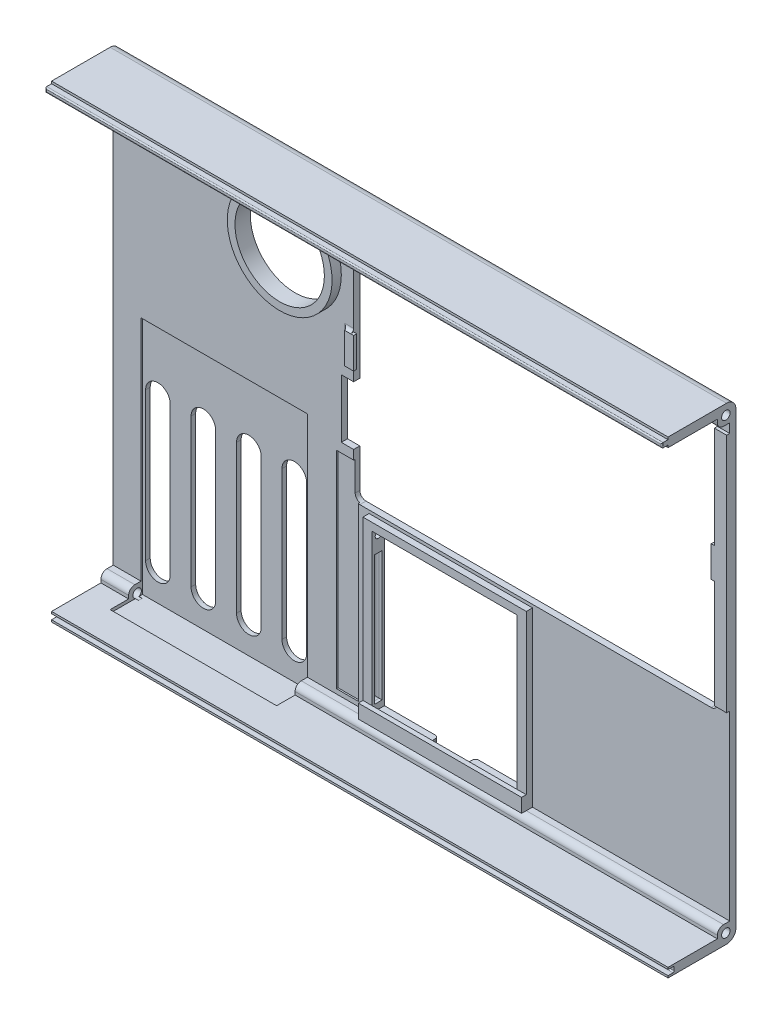
SolidWorks part; units mm, degrees
ref_plane "Front Plane" through (0, 0, 0) normal (0, 0, 1) x (1, 0, 0)
ref_plane "Top Plane" through (0, 0, 0) normal (0, 1, 0) x (1, 0, 0)
ref_plane "Right Plane" through (0, 0, 0) normal (1, 0, 0) x (0, 0, -1)
sketch "Sketch1" plane through (0, 0, 0) normal (0, 0, 1) x (1, 0, 0)
  line L1 (105, -90.3987) -> (-95, -90.3987)
  line L2 (105, -90.3987) -> (105, 61.6013)
  line L3 (105, 61.6013) -> (-95, 61.6013)
  line L4 (-95, -90.3987) -> (-95, 61.6013)
  line L5 (105, -90.3987) -> (-95, 61.6013) construction
  line L6 (105, 61.6013) -> (-95, -90.3987) construction
  point P0 (5, -14.3987)
  dimension "D1" = 200
  dimension "D2" = 152
extrude "body" add sketch "Sketch1" along normal blind 2
sketch "Sketch3" plane through (0, 0, 0) normal (0, 0, -1) x (-1, 0, 0)
  line L0 (95, -54.3987) -> (-105, -54.3987) construction
  line L1 (95, 61.6013) -> (95, -90.3987) construction
  line L2 (-105, -90.3987) -> (-105, 61.6013) construction
  line L3 (66.25, -78.3987) -> (66.25, -30.3987) construction
  line L4 (62.25, -78.3987) -> (62.25, -30.3987)
  line L5 (70.25, -78.3987) -> (70.25, -30.3987)
  line L6 (95, -30.3987) -> (-105, -30.3987) construction
  line L7 (81, -78.3987) -> (81, -30.3987) construction
  line L8 (95, -78.3987) -> (-105, -78.3987) construction
  line L9 (77, -78.3987) -> (77, -30.3987)
  line L10 (85, -78.3987) -> (85, -30.3987)
  line L11 (51.5, -78.3987) -> (51.5, -30.3987) construction
  line L12 (47.5, -78.3987) -> (47.5, -30.3987)
  line L13 (55.5, -78.3987) -> (55.5, -30.3987)
  line L14 (36.75, -78.3987) -> (36.75, -30.3987) construction
  line L15 (32.75, -78.3987) -> (32.75, -30.3987)
  line L16 (40.75, -78.3987) -> (40.75, -30.3987)
  line L17 (95, -90.3987) -> (95, 61.6013) construction
  line L18 (-105, 61.6013) -> (95, 61.6013) construction
  line L19 (95, -90.3987) -> (-105, -90.3987) construction
  line L20 (-105, -90.3987) -> (-105, 61.6013) construction
  circle A0 centre (38, 34.1013) radius 14.5
  arc A1 (62.25, -78.3987) -> (70.25, -78.3987) centre (66.25, -78.3987) ccw
  arc A2 (70.25, -30.3987) -> (62.25, -30.3987) centre (66.25, -30.3987) ccw
  arc A3 (77, -78.3987) -> (85, -78.3987) centre (81, -78.3987) ccw
  arc A4 (85, -30.3987) -> (77, -30.3987) centre (81, -30.3987) ccw
  arc A5 (47.5, -78.3987) -> (55.5, -78.3987) centre (51.5, -78.3987) ccw
  arc A6 (55.5, -30.3987) -> (47.5, -30.3987) centre (51.5, -30.3987) ccw
  arc A7 (32.75, -78.3987) -> (40.75, -78.3987) centre (36.75, -78.3987) ccw
  arc A8 (40.75, -30.3987) -> (32.75, -30.3987) centre (36.75, -30.3987) ccw
  point P10 (66.25, -54.3987)
  point P21 (81, -54.3987)
  point P27 (51.5, -54.3987)
  point P34 (36.75, -54.3987)
  dimension "D1" = 29
  dimension "D2" = 27.5
  dimension "D3" = 57
  dimension "D4" = 10
  dimension "D5" = 12
  dimension "D6" = 24
  dimension "D7" = 6.75
  dimension "D8" = 8
  dimension "D9" = 8
  dimension "D10" = 8
  dimension "D11" = 8
  dimension "D12" = 6.75
  dimension "D13" = 52.25
  dimension "D14" = 6.75
extrude "fan_exhaust_grill" cut sketch "Sketch3" against normal through all
sketch "Sketch12" plane through (0, 0, 2) normal (0, 0, 1) x (1, 0, 0)
  line L0 (-95, -90.3987) -> (-95, 61.6013) construction
  line L1 (105, -90.3987) -> (-95, -90.3987)
  line L2 (105, -90.3987) -> (105, -84.3987)
  line L3 (105, -84.3987) -> (-95, -84.3987)
  line L4 (-95, -90.3987) -> (-95, -84.3987)
  line L6 (105, 61.6013) -> (-95, 61.6013)
  line L7 (105, 61.6013) -> (105, 55.6013)
  line L8 (105, 55.6013) -> (-95, 55.6013)
  line L9 (-95, 61.6013) -> (-95, 55.6013)
  dimension "D1" = 6
  dimension "D2" = 6
extrude "side_walls" add sketch "Sketch12" along normal blind 20
sketch "Sketch14" plane through (105, 0, 0) normal (1, 0, 0) x (0, 0, -1)
  line L0 (-22, -90.3987) -> (0, -90.3987) construction
  line L1 (0, -90.3987) -> (0, 61.6013) construction
  line L2 (-22, 61.6013) -> (0, 61.6013) construction
  circle A0 centre (-3.25, -87.1487) radius 1.375
  circle A1 centre (-3.25, 58.3513) radius 1.375
  dimension "D1" = 2.75
  dimension "D2" = 2.75
  dimension "D3" = 3.25
  dimension "D4" = 3.25
  dimension "D5" = 3.25
  dimension "D6" = 3.25
  dimension "D7" = 145.5
extrude "mount_holes_l" cut sketch "Sketch14" against normal blind 10 and the other way through all
sketch "Sketch16" plane through (-95, 0, 0) normal (-1, 0, 0) x (0, 0, 1)
  line L0 (0, -90.3987) -> (0, 61.6013) construction
  line L2 (22, 61.6013) -> (0, 61.6013) construction
  line L3 (22, -90.3987) -> (0, -90.3987) construction
  circle A0 centre (3.25, -87.1487) radius 1.375
  circle A1 centre (3.25, 58.3513) radius 1.375
  dimension "D1" = 2.75
  dimension "D4" = 2.75
  dimension "D2" = 3.25
  dimension "D3" = 3.25
  dimension "D5" = 3.25
  dimension "D6" = 3.25
extrude "mount_holes_r" cut sketch "Sketch16" against normal blind 10
sketch "Sketch18" plane through (105, 0, 0) normal (1, 0, 0) x (0, 0, -1)
  line L1 (-22, -84.3987) -> (-6, -84.3987)
  line L2 (-22, -84.3987) -> (-22, -87.3987)
  line L3 (-22, -87.3987) -> (-6, -87.3987)
  line L4 (-6, -84.3987) -> (-6, -87.3987)
  line L5 (-22, 55.6013) -> (-6, 55.6013)
  line L6 (-22, 55.6013) -> (-22, 58.6013)
  line L7 (-22, 58.6013) -> (-6, 58.6013)
  line L8 (-6, 55.6013) -> (-6, 58.6013)
  dimension "D1" = 3
  dimension "D2" = 16
  dimension "D3" = 3
  dimension "D4" = 16
extrude "wall_reduce" cut sketch "Sketch18" against normal through all
sketch "Sketch19" plane through (0, 0, 22) normal (0, 0, 1) x (1, 0, 0)
  line L0 (-95, -90.3987) -> (-95, 61.6013) construction
  line L1 (-95, -89.7487) -> (105, -89.7487)
  line L2 (-95, -89.7487) -> (-95, -88.0487)
  line L3 (-95, -88.0487) -> (105, -88.0487)
  line L4 (105, -89.7487) -> (105, -88.0487)
  line L5 (105, -90.3987) -> (105, 61.6013) construction
  line L6 (-95, -90.3987) -> (105, -90.3987) construction
  line L7 (-95, -87.3987) -> (105, -87.3987) construction
  dimension "D1" = 0.65
  dimension "D2" = 1.7
  dimension "D3" = 0.65
extrude "groove" cut sketch "Sketch19" against normal blind 2
sketch "Sketch20" plane through (0, 0, 22) normal (0, 0, 1) x (1, 0, 0)
  line L0 (-95, -90.3987) -> (-95, 61.6013) construction
  line L1 (-95, 59.3513) -> (105, 59.3513)
  line L2 (-95, 59.3513) -> (-95, 60.8513)
  line L3 (-95, 60.8513) -> (105, 60.8513)
  line L4 (105, 59.3513) -> (105, 60.8513)
  line L5 (105, -90.3987) -> (105, 61.6013) construction
  line L6 (105, 61.6013) -> (-95, 61.6013) construction
  dimension "D1" = 0.75
  dimension "D2" = 1.5
extrude "notch" add sketch "Sketch20" along normal blind 2
sketch "Sketch21" plane through (0, 0, 2) normal (0, 0, 1) x (1, 0, 0)
  line L0 (105, -90.3987) -> (105, 61.6013) construction
  line L1 (101, -27.3987) -> (-17, -27.3987)
  line L2 (101, -27.3987) -> (101, 55.1013)
  line L3 (101, 55.1013) -> (-17, 55.1013)
  line L4 (-17, -27.3987) -> (-17, 55.1013)
  line L5 (105, 61.6013) -> (-95, 61.6013) construction
  dimension "D1" = 118
  dimension "D2" = 82.5
  dimension "D3" = 4
  dimension "D4" = 6.5
extrude "batt_cut" cut sketch "Sketch21" against normal through all
fillet "Fillet1" radius 3 2 edges at (5, -90.3987, 0) (5, 61.6013, 0)
fillet "Fillet2" radius 2 2 edges at (5, -84.3987, 6) (5, 55.6013, 6)
fillet "Fillet3" radius 0.4 6 edges at (5, 60.8513, 24) (105, 60.1013, 24) (5, 59.3513, 24) (-95, 60.1013, 24) (5, -89.7487, 20) (5, -88.0487, 20)
fillet "Fillet4" radius 2 4 edges at (-17, -27.3987, 1) (101, -27.3987, 1) (101, 55.1013, 1) (-17, 55.1013, 1)
sketch "Sketch22" plane through (0, 0, 2) normal (0, 0, 1) x (1, 0, 0)
  circle A0 centre (-38, 34.1013) radius 14.5
  circle A1 centre (-38, 34.1013) radius 17
  dimension "D1" = 29
  dimension "D2" = 34
extrude "fan_hole_supp" add sketch "Sketch22" along normal blind 3
sketch "Sketch23" plane through (0, 0, 2) normal (0, 0, 1) x (1, 0, 0)
  line L0 (105, -90.3987) -> (105, 61.6013) construction
  line L1 (105, 52.6013) -> (101, 52.6013)
  line L2 (105, 52.6013) -> (105, -25.3987)
  line L3 (105, -25.3987) -> (101, -25.3987)
  line L4 (101, 52.6013) -> (101, -25.3987)
  arc A0 (99, -27.3987) -> (101, -25.3987) centre (99, -25.3987) ccw construction
  dimension "D1" = 78
  dimension "D2" = 4
extrude "batt_cut_supp" add sketch "Sketch23" along normal blind 1
sketch "Sketch24" plane through (0, 0, 2) normal (0, 0, 1) x (1, 0, 0)
  line L0 (-95, -90.3987) -> (-95, 61.6013) construction
  line L1 (-86, -10.3987) -> (-32, -10.3987)
  line L2 (-86, -10.3987) -> (-86, -88.3987)
  line L3 (-86, -88.3987) -> (-32, -88.3987)
  line L4 (-32, -10.3987) -> (-32, -88.3987)
  line L5 (-95, -90.3987) -> (105, -90.3987) construction
  line L7 (-22.5, -15.8987) -> (-15.5, -15.8987)
  line L8 (-22.5, -15.8987) -> (-22.5, -82.8987)
  line L9 (-22.5, -82.8987) -> (-15.5, -82.8987)
  line L10 (-15.5, -15.8987) -> (-15.5, -82.8987)
  dimension "D1" = 9
  dimension "D2" = 2
  dimension "D3" = 54
  dimension "D4" = 78
  dimension "D5" = 9.5
  dimension "D6" = 7
  dimension "D7" = 67
  dimension "D8" = 5.5
  dimension "D9" = 5.5
extrude "Cut-Extrude1" cut sketch "Sketch24" against normal blind 10.5 from offset 10
sketch "Sketch25" plane through (0, 0, 2) normal (0, 0, 1) x (1, 0, 0)
  line L7 (-17, 53.1013) -> (-17, -15.8987) construction
  line L8 (-17, 6.1013) -> (-21, 6.1013)
  line L9 (-17, 6.1013) -> (-17, -12.8987)
  line L10 (-17, -12.8987) -> (-21, -12.8987)
  line L11 (-21, 6.1013) -> (-21, -12.8987)
  line L12 (-15, -27.3987) -> (99, -27.3987) construction
  dimension "D1" = 14.5
  dimension "D2" = 19
  dimension "D3" = 4
extrude "Cut-Extrude2" cut sketch "Sketch25" against normal through all
sketch "Sketch26" plane through (0, 0, 2) normal (0, 0, 1) x (1, 0, 0)
  line L0 (-17, 53.1013) -> (-17, 6.1013) construction
  line L1 (-17, 20.1013) -> (-19, 20.1013)
  line L2 (-17, 20.1013) -> (-17, 10.1013)
  line L3 (-17, 10.1013) -> (-19, 10.1013)
  line L4 (-19, 20.1013) -> (-19, 10.1013)
  line L10 (99, 55.1013) -> (-15, 55.1013) construction
  dimension "D4" = 2
  dimension "D5" = 10
  dimension "D6" = 35
extrude "Boss-Extrude1" add sketch "Sketch26" along normal blind 1
sketch "Sketch27" plane through (-17, 0, 0) normal (1, 0, 0) x (0, 0, -1)
  line L0 (-3, 10.1013) -> (-3, 20.1013) construction
  line L1 (-3, 20.1013) -> (-2, 20.1013)
  line L2 (-3, 20.1013) -> (-3, 10.1013)
  line L3 (-3, 10.1013) -> (-2, 10.1013)
  line L4 (-2, 20.1013) -> (-2, 10.1013)
  line L5 (-3, 20.1013) -> (-2, 20.1013) construction
extrude "Boss-Extrude2" add sketch "Sketch27" along normal blind 1
sketch "Sketch28" plane through (101, 0, 0) normal (-1, 0, 0) x (0, 0, 1)
  line L0 (0, -25.3987) -> (0, 53.1013) construction
  line L1 (2, 9.6013) -> (3, 9.6013)
  line L2 (2, 9.6013) -> (2, 19.6013)
  line L3 (2, 19.6013) -> (3, 19.6013)
  line L4 (3, 9.6013) -> (3, 19.6013)
  line L5 (3, 52.6013) -> (2, 52.6013) construction
  dimension "D1" = 1
  dimension "D2" = 2
  dimension "D3" = 10
  dimension "D4" = 33
extrude "Boss-Extrude3" add sketch "Sketch28" along normal blind 1
fillet "Fillet5" radius 1 3 edges at (-18, 20.1013, 2) (-18, 10.1013, 2) (-19, 15.1013, 2)
sketch "Sketch29" plane through (0, 0, 2) normal (0, 0, 1) x (1, 0, 0)
  line L1 (-9, -30.8987) -> (38, -30.8987)
  line L2 (-9, -30.8987) -> (-9, -81.8987)
  line L3 (-9, -81.8987) -> (38, -81.8987)
  line L4 (38, -30.8987) -> (38, -81.8987)
  line L5 (105, -90.3987) -> (105, 61.6013) construction
  line L7 (-95, -90.3987) -> (105, -90.3987) construction
  dimension "D1" = 67
  dimension "D2" = 47
  dimension "D3" = 51
  dimension "D4" = 8.5
extrude "stand_cut" cut sketch "Sketch29" against normal through all
sketch "Sketch30" plane through (0, 0, 2) normal (0, 0, 1) x (1, 0, 0)
  line L0 (-9, -81.8987) -> (38, -30.8987) construction
  line L1 (38, -30.8987) -> (-9, -30.8987) construction
  line L2 (38, -81.8987) -> (38, -30.8987) construction
  line L3 (-9, -30.8987) -> (38, -81.8987) construction
  line L5 (41, -84.3987) -> (-12, -84.3987)
  line L6 (41, -84.3987) -> (41, -28.3987)
  line L7 (41, -28.3987) -> (-12, -28.3987)
  line L8 (-12, -84.3987) -> (-12, -28.3987)
  line L9 (41, -84.3987) -> (-12, -28.3987) construction
  line L10 (41, -28.3987) -> (-12, -84.3987) construction
  line L11 (38, -81.8987) -> (-9, -81.8987)
  line L12 (38, -81.8987) -> (38, -30.8987)
  line L13 (38, -30.8987) -> (-9, -30.8987)
  line L14 (-9, -81.8987) -> (-9, -30.8987)
  line L15 (38, -81.8987) -> (-9, -30.8987) construction
  line L16 (38, -30.8987) -> (-9, -81.8987) construction
  point P11 (14.5, -56.3987)
  point P16 (14.5, -56.3987)
  dimension "D1" = 3
  dimension "D2" = 2.5
extrude "stand_extra_support" add sketch "Sketch30" along normal blind 2
sketch "Sketch31" plane through (-9, 0, 0) normal (1, 0, 0) x (0, 0, -1)
  line L0 (-2, -23.813) -> (-2, -81.8987) construction
  line L1 (0, -81.8987) -> (-4, -81.8987) construction
  line L2 (0, -30.8987) -> (0, -81.8987) construction
  line L3 (-0.75, -79.8987) -> (-3.25, -79.8987)
  line L4 (-0.75, -79.8987) -> (-0.75, -37.8987)
  line L5 (-0.75, -37.8987) -> (-3.25, -37.8987)
  line L6 (-3.25, -79.8987) -> (-3.25, -37.8987)
  line L7 (-0.75, -79.8987) -> (-3.25, -37.8987) construction
  line L8 (-0.75, -37.8987) -> (-3.25, -79.8987) construction
  line L9 (0, -30.8987) -> (-4, -30.8987) construction
  circle A0 centre (-2, -32.8987) radius 1
  point P4 (-2, -58.8987)
  dimension "D6" = 2
  dimension "D1" = 2
  dimension "D2" = 42
  dimension "D3" = 2.5
  dimension "D4" = 0.75
  dimension "D5" = 2
extrude "stand_right_groove" cut sketch "Sketch31" against normal blind 2
sketch "Sketch32" plane through (38, 0, 0) normal (-1, 0, 0) x (0, 0, 1)
  line L0 (2, -81.8987) -> (2, -30.8421) construction
  line L1 (0, -81.8987) -> (4, -81.8987) construction
  line L2 (0, -30.8987) -> (4, -30.8987) construction
  line L3 (3.25, -37.8987) -> (0.75, -37.8987)
  line L4 (3.25, -37.8987) -> (3.25, -79.8987)
  line L5 (3.25, -79.8987) -> (0.75, -79.8987)
  line L6 (0.75, -37.8987) -> (0.75, -79.8987)
  line L7 (3.25, -37.8987) -> (0.75, -79.8987) construction
  line L8 (3.25, -79.8987) -> (0.75, -37.8987) construction
  circle A0 centre (2, -32.8987) radius 1
  point P4 (2, -58.8987)
  dimension "D5" = 2
  dimension "D1" = 2.5
  dimension "D2" = 42
  dimension "D3" = 2
  dimension "D4" = 2
extrude "stand_left_groove" cut sketch "Sketch32" against normal blind 2
fillet "Fillet6" radius 1 8 edges at (40, -37.8987, 2) (40, -58.8987, 3.25) (40, -79.8987, 2) (40, -58.8987, 0.75) (-11, -37.8987, 2) (-11, -58.8987, 0.75) (-11, -79.8987, 2) (-11, -58.8987, 3.25)
sketch "Sketch33" plane through (0, 0, 0) normal (0, 0, -1) x (-1, 0, 0)
  line L0 (-14.5, -81.8987) -> (-14.5, -30.8987) construction
  line L1 (9, -81.8987) -> (-38, -81.8987) construction
  line L2 (-38, -30.8987) -> (9, -30.8987) construction
  line L3 (-105, -87.3987) -> (95, -87.3987) construction
  line L4 (-8.5, -84.8987) -> (-20.5, -84.8987)
  line L5 (-8.5, -84.8987) -> (-8.5, -81.8987)
  line L6 (-8.5, -81.8987) -> (-20.5, -81.8987)
  line L7 (-20.5, -84.8987) -> (-20.5, -81.8987)
  line L8 (-8.5, -84.8987) -> (-20.5, -81.8987) construction
  line L9 (-8.5, -81.8987) -> (-20.5, -84.8987) construction
  point P6 (-14.5, -83.3987)
  dimension "D1" = 2.5
  dimension "D2" = 3
  dimension "D3" = 12
extrude "finger_notch" cut sketch "Sketch33" against normal blind 2.5
fillet "Fillet7" radius 1 6 edges at (8.5, -83.3987, 2.5) (8.5, -83.3987, 0) (20.5, -83.3987, 0) (14.5, -84.8987, 0) (20.5, -83.3987, 2.5) (14.5, -84.8987, 2.5)
sketch "Sketch34" plane through (0, 0, 4) normal (0, 0, 1) x (1, 0, 0)
  line L0 (41, -84.3987) -> (41, -28.3987) construction
  line L1 (-12, -84.3987) -> (41, -84.3987)
  line L2 (-12, -84.3987) -> (-12, -81.8987)
  line L3 (-12, -81.8987) -> (41, -81.8987)
  line L4 (41, -84.3987) -> (41, -81.8987)
  dimension "D1" = 2.5
extrude "back_lid_ext" add sketch "Sketch34" along normal blind 1.5
sketch "Sketch35" plane through (0, -81.8987, 0) normal (0, 1, 0) x (1, 0, 0)
  line L1 (-12, -5.5) -> (41, -5.5)
  line L2 (-12, -5.5) -> (-12, -4)
  line L3 (-12, -4) -> (41, -4)
  line L4 (41, -5.5) -> (41, -4)
extrude "stand_lid" add sketch "Sketch35" along normal blind 2
